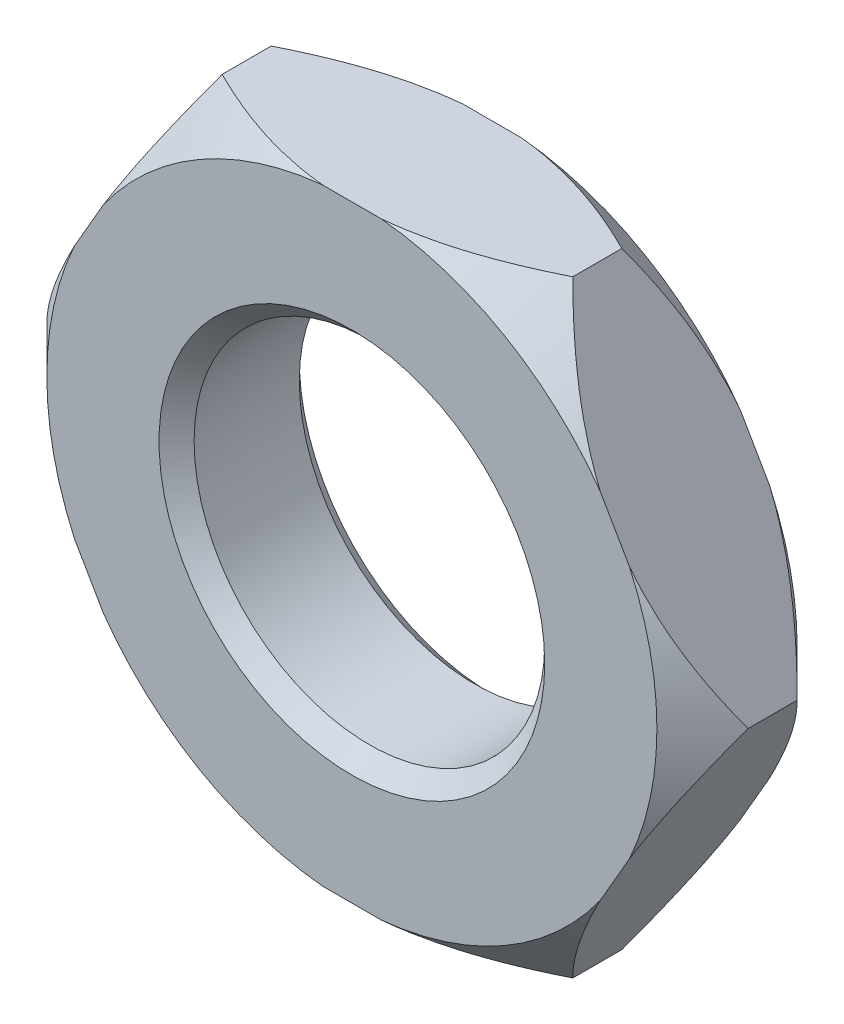
SolidWorks part; units mm, degrees
ref_plane "Front Plane" through (0, 0, 0) normal (0, 0, 1) x (1, 0, 0)
ref_plane "Top Plane" through (0, 0, 0) normal (0, 1, 0) x (1, 0, 0)
ref_plane "Right Plane" through (0, 0, 0) normal (1, 0, 0) x (0, 0, -1)
sketch "Sketch1" plane through (0, 0, 0) normal (0, 0, 1) x (1, 0, 0)
  line L1 (-10, 0) -> (-5, -8.6603)
  line L2 (-5, -8.6603) -> (5, -8.6603)
  line L3 (5, -8.6603) -> (10, 0)
  line L4 (10, 0) -> (5, 8.6603)
  line L5 (5, 8.6603) -> (-5, 8.6603)
  line L6 (-5, 8.6603) -> (-10, 0)
  circle A0 centre (0, 0) radius 10 construction
  dimension "D1" = 20
extrude "Boss-Extrude1" add sketch "Sketch1" along normal mid plane 4
sketch "Sketch2" plane through (0, 0, -2) normal (0, 0, 1) x (1, 0, 0)
  circle A0 centre (0, 0) radius 5
  dimension "D1" = 10
extrude "Cut-Extrude1" cut sketch "Sketch2" along normal through all
cosmetic thread "Cosmetic Thread1" parameters "D2"=12
sketch "Sketch8" plane through (0, 0, 0) normal (0, 1, 0) x (1, 0, 0)
  line L0 (-8.6, -2.1) -> (-10.1, -2.1)
  line L1 (-10.1, -2.1) -> (-10.1, -0.6)
  line L2 (-10.1, -0.6) -> (-8.6, -2.1)
  line L4 (-10, -2) -> (-10, 2) construction
  line L5 (-5, -2) -> (-10, -2) construction
  dimension "D1" = 1.5
  dimension "D2" = 1.5
  dimension "D3" = 0.1
  dimension "D4" = 0.1
ref_axis "Axis1" through (0, 0, -7.705) along (0, 0, 1)
revolve "Cut-Revolve1" cut sketch "Sketch8" angle 360 about axis through (0, 0, -7.705) along (0, 0, 1)
ref_axis "Axis2" through (0, 0, -7.7832) along (0, 0, 1)
mirror "Mirror1" about plane through (0, 0, 0) normal (0, 0, 1) of "Cut-Revolve1"
chamfer "Chamfer1" distance 0.5 angle 45 2 edges at (5, 0, -2) (5, 0, 2)
